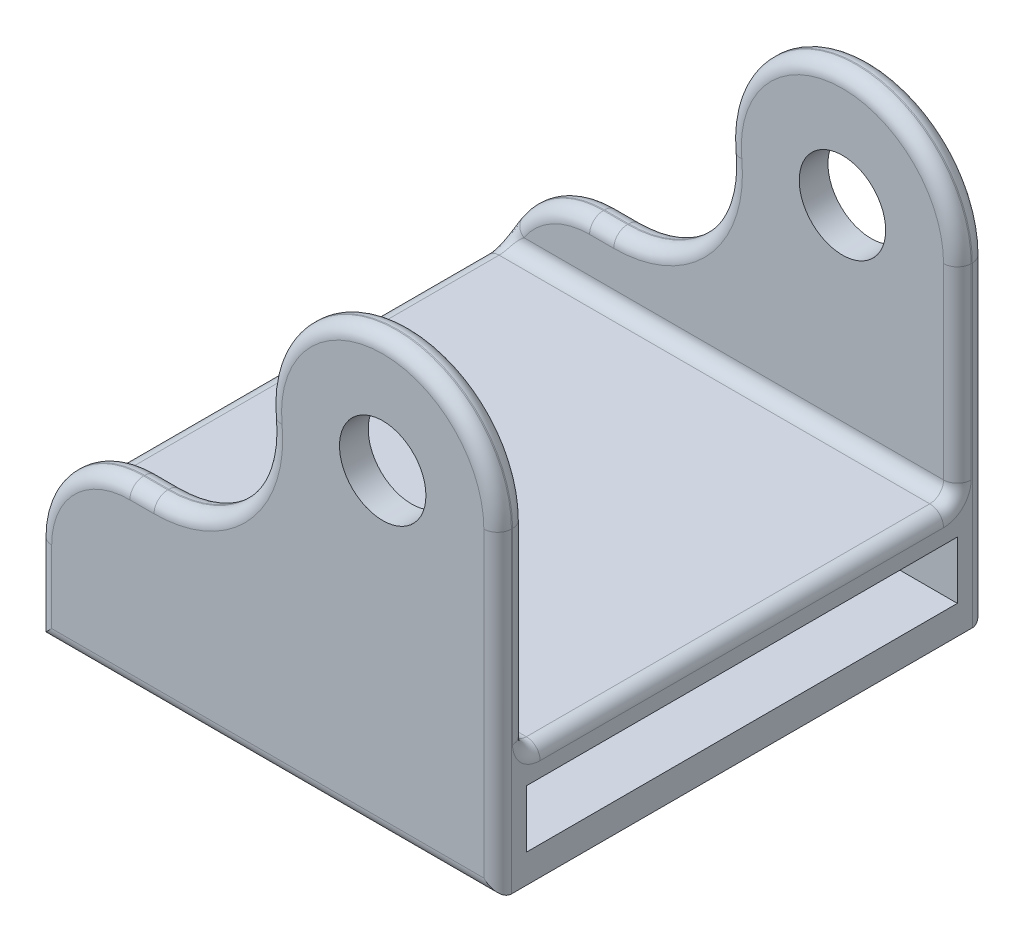
SolidWorks part; units mm, degrees
material "Chrome Stainless Steel"
ref_plane "Front" through (0, 0, 0) normal (0, 0, 1) x (1, 0, 0)
ref_plane "Top" through (0, 0, 0) normal (0, 1, 0) x (1, 0, 0)
ref_plane "Right" through (0, 0, 0) normal (1, 0, 0) x (0, 0, -1)
sketch "Sketch1" plane through (0, 0, 0) normal (0, 0, 1) x (1, 0, 0)
  line L0 (0, 0) -> (-25.4, 0)
  line L1 (0, 0) -> (0, 12.7)
  line L2 (-18.9863, 5.08) -> (-20.32, 5.08)
  arc A0 (0, 12.7) -> (-12.6682, 12.065) centre (-6.35, 12.7) ccw
  arc A1 (-12.6682, 12.065) -> (-18.9863, 5.08) centre (-18.9863, 11.43) cw
  arc A2 (-20.32, 5.08) -> (-25.4, 0) centre (-20.32, 0) ccw
  dimension "D2" = 12.7
  dimension "D3" = 6.35
  dimension "D4" = 5.08
  dimension "D5" = 6.35
  dimension "D1" = 25.4
extrude "Extrude1" add sketch "Sketch1" along normal mid plane 26.9875
shell "Shell1" thickness 1.5875 removed face at (-6.501, 15.7123, 0) removed face at (-15.0522, 7.8714, 0) removed face at (-23.3861, 3.0661, 0) removed face at (-19.6532, 5.08, 0)
sketch "Sketch2" plane through (0, 0, 13.4937) normal (0, 0, 1) x (1, 0, 0)
  circle A0 centre (-6.35, 12.7) radius 2.3876
  dimension "D1" = 4.7752
extrude "Cut-Extrude1" cut sketch "Sketch2" against normal through all
sketch "Sketch3" plane through (0, 0, 0) normal (0, -1, 0) x (1, 0, 0)
  line L4 (-25.4, -13.4937) -> (0, -13.4937)
  line L5 (0, -13.4937) -> (0, 13.4937)
  line L6 (0, 13.4937) -> (-25.4, 13.4937)
  line L7 (-25.4, 13.4937) -> (-25.4, -13.4937)
  line L8 (-25.4, -13.4937) -> (0, -13.4937)
  line L9 (0, -13.4937) -> (0, 13.4937)
  line L10 (0, 13.4937) -> (-25.4, 13.4937)
  line L11 (-25.4, 13.4937) -> (-25.4, -13.4937)
  dimension "D1" = 0
extrude "Extrude2" add sketch "Sketch3" along normal blind 4.7625
sketch "Sketch4" plane through (0, 0, 0) normal (1, 0, 0) x (0, 0, -1)
  line L0 (11.9062, 1.5875) -> (11.9062, 12.7) construction
  line L1 (-11.9062, 0) -> (11.9062, 0)
  line L2 (-11.9062, 0) -> (-11.9062, -3.175)
  line L3 (-11.9062, -3.175) -> (11.9062, -3.175)
  line L4 (11.9062, 0) -> (11.9062, -3.175)
  line L5 (-11.9062, 1.5875) -> (-11.9062, 12.7) construction
  line L7 (13.4937, -4.7625) -> (-13.4937, -4.7625) construction
  dimension "D1" = 3.175
  dimension "D2" = 1.5875
extrude "Cut-Extrude2" cut sketch "Sketch4" against normal through all
fillet "Fillet1" radius 0.762 28 edges at (0, 7.1437, 11.9062) (-6.6679, 19.042, 11.9062) (-14.2771, 7.1703, 11.9062) (-19.6532, 5.08, 11.9062) (0, 7.1437, -11.9062) (-6.6679, 19.042, -11.9062) (-14.2771, 7.1703, -11.9062) (-19.6532, 5.08, -11.9062) (0, 3.9688, 13.4937) (-6.6679, 19.042, 13.4937) (-14.2771, 7.1703, 13.4937) (-19.6532, 5.08, 13.4937) (-25.4, -2.3813, 13.4937) (0, 3.9688, -13.4937) (-6.6679, 19.042, -13.4937) (-14.2771, 7.1703, -13.4937) (-19.6532, 5.08, -13.4937) (-23.9121, 3.5921, -13.4937) (-12.7, -4.7625, -13.4937) (-12.7, -4.7625, 13.4937) (-12.5728, 1.5875, -11.9062) (-12.5728, 1.5875, 11.9062) (0, 1.5875, 0) (-25.1456, 1.5875, 0) (-23.2984, 4.1153, 11.9062) (-23.2984, 4.1153, -11.9062) (-23.9121, 3.5921, 13.4937) (-25.4, -2.3813, -13.4937)
